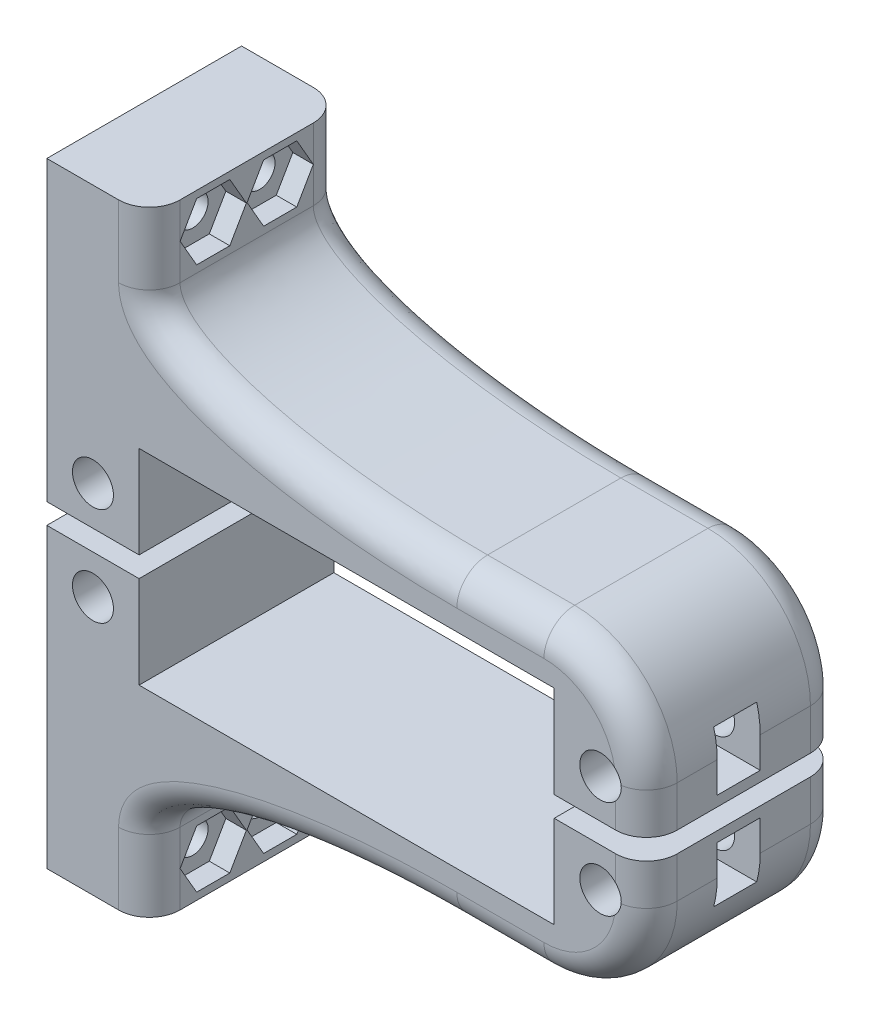
SolidWorks part; units mm, degrees
material "20% infill ABS"
ref_plane "Front" through (0, 0, 0) normal (0, 0, 1) x (1, 0, 0)
ref_plane "Top" through (0, 0, 0) normal (0, 1, 0) x (1, 0, 0)
ref_plane "Right" through (0, 0, 0) normal (1, 0, 0) x (0, 0, -1)
sketch "Sketch1" plane through (0, 0, 0) normal (0, 0, 1) x (1, 0, 0)
  line L1 (-9, -5) -> (49.5, -5)
  line L3 (-9, 25) -> (49.5, 25)
  line L4 (0, 0) -> (40.5, 0)
  line L5 (40.5, 0) -> (40.5, 20)
  line L6 (40.5, 20) -> (0, 20)
  line L7 (0, 20) -> (0, 0)
  line L8 (0, 0) -> (40.5, 0)
  line L9 (40.5, 0) -> (40.5, 20)
  line L10 (40.5, 20) -> (0, 20)
  line L11 (0, 20) -> (0, 0)
  line L12 (49.5, -5) -> (49.5, 25)
  line L13 (47.5, 20) -> (47.5, 0) construction
  line L17 (-9, 25) -> (-9, -5)
  dimension "D2" = 5
  dimension "D3" = 5
  dimension "D4" = 2
  dimension "D5" = 9
  dimension "D1" = 0
extrude "Boss-Extrude1" add sketch "Sketch1" against normal blind 19
ref_plane "Plane1" through (0, 0, -9) normal (0, 0, 1) x (1, 0, 0)
sketch "Sketch2" plane through (0, 0, -19) normal (0, 0, -1) x (-1, 0, 0)
  circle A0 centre (-45, 14.8) radius 2 construction
  circle A1 centre (-45, 5.2) radius 2 construction
  circle A2 centre (4.5, 14.8) radius 2 construction
  circle A3 centre (4.5, 5.2) radius 2 construction
  circle A4 centre (-45, 14.8) radius 2
  circle A5 centre (-45, 5.2) radius 2
  circle A6 centre (4.5, 14.8) radius 2
  circle A7 centre (4.5, 5.2) radius 2
extrude "Cut-Extrude1" cut sketch "Sketch2" against normal through all
sketch "Sketch3" plane through (0, 0, -9) normal (0, 0, 1) x (1, 0, 0)
  line L0 (49.5, 10) -> (-9, 10) construction
  line L7 (49.5, -5) -> (49.5, 25) construction
  line L8 (-9, 25) -> (-9, -5) construction
  line L9 (43.3834, 2.4) -> (41.7668, 5.2)
  line L10 (20.25, 20) -> (20.25, 0) construction
  line L13 (49.5, 17.6) -> (43.3834, 17.6)
  line L14 (41.7668, 5.2) -> (43.3834, 8)
  line L15 (43.3834, 17.6) -> (41.7668, 14.8)
  line L16 (41.7668, 14.8) -> (43.3834, 12)
  line L17 (43.3834, 12) -> (49.5, 12)
  line L28 (40.5, 20) -> (0, 20) construction
  line L29 (0, 0) -> (40.5, 0) construction
  line L30 (49.5, 17.6) -> (49.5, 12)
  line L33 (48.2332, 14.8) -> (47.4249, 16.2) [skipped]
  line L34 (46.6166, 12) -> (47.4249, 13.4) [skipped]
  line L35 (49.5, 17.6) -> (49.5, 12)
  line L36 (43.3834, 8) -> (49.5, 8)
  line L37 (49.5, 2.4) -> (49.5, 8)
  line L38 (49.5, 2.4) -> (43.3834, 2.4)
  line L39 (-1.2668, 14.8) -> (-2.8834, 12)
  line L40 (-2.8834, 17.6) -> (-1.2668, 14.8)
  line L41 (-9, 17.6) -> (-2.8834, 17.6)
  line L42 (-9, 17.6) -> (-9, 12)
  line L43 (-2.8834, 12) -> (-9, 12)
  line L44 (-2.8834, 8) -> (-9, 8)
  line L45 (-9, 2.4) -> (-9, 8)
  line L46 (-9, 2.4) -> (-2.8834, 2.4)
  line L47 (-2.8834, 2.4) -> (-1.2668, 5.2)
  line L48 (-1.2668, 5.2) -> (-2.8834, 8)
  circle A0 centre (45, 14.8) radius 2.8 construction
  dimension "D1" = 5.6
extrude "Cut-Extrude4" cut sketch "Sketch3" against normal mid plane 4.2 contours L43 L39 L40 L41 L42 | L47 L48 L44 L45 L46 | L38 L37 L36 L14 L9 | L30 L13 L15 L16 L17 | L41 L40 L39 L43 L42 region at (46.0218, 5.2, -9) region at (46.0218, 14.8, -9) region at (-5.5218, 14.8, -9) region at (-5.5218, 5.2, -9)
sketch "Sketch4" plane through (-9, 0, 0) normal (-1, 0, 0) x (0, 0, 1)
  line L0 (-19, 25) -> (-19, -5) construction
  line L1 (0, 25) -> (-19, 25)
  line L2 (0, 25) -> (0, 40)
  line L3 (0, 40) -> (-19, 40)
  line L4 (-19, 25) -> (-19, 40)
  dimension "D1" = 15
extrude "Boss-Extrude2" add sketch "Sketch4" against normal blind 10
fillet "Fillet1" radius 8 1 edges at (1, 25, -9.5) second distance 30 first distance on face at (1, 32.5, -9.5)
sketch "Sketch6" plane through (1, 0, 0) normal (1, 0, 0) x (0, 0, -1)
  line L0 (19, 36.5) -> (0, 36.5) construction
  line L1 (16, 36.5) -> (14.3834, 39.3)
  line L2 (14.3834, 39.3) -> (11.1503, 39.3)
  line L3 (11.1503, 39.3) -> (9.5337, 36.5)
  line L4 (9.5337, 36.5) -> (11.1503, 33.7)
  line L5 (11.1503, 33.7) -> (14.3834, 33.7)
  line L6 (14.3834, 33.7) -> (16, 36.5)
  line L7 (19, 40) -> (19, 33) construction
  line L8 (0, 33) -> (0, 40) construction
  line L9 (9.5, 40) -> (9.5, 33) construction
  line L10 (0, 40) -> (19, 40) construction
  line L11 (0, 33) -> (19, 33) construction
  line L12 (4.6166, 33.7) -> (3, 36.5)
  line L13 (7.8497, 33.7) -> (4.6166, 33.7)
  line L14 (9.4663, 36.5) -> (7.8497, 33.7)
  line L15 (7.8497, 39.3) -> (9.4663, 36.5)
  line L16 (4.6166, 39.3) -> (7.8497, 39.3)
  line L17 (3, 36.5) -> (4.6166, 39.3)
  circle A0 centre (12.7668, 36.5) radius 1.5
  circle A1 centre (12.7668, 36.5) radius 2.8 construction
  circle A2 centre (6.2332, 36.5) radius 1.5
  dimension "D2" = 3
  dimension "D1" = 5.6
  dimension "D3" = 3
extrude "Cut-Extrude5" cut sketch "Sketch6" against normal through all contours A0 | A2
extrude "Cut-Extrude6" cut sketch "Sketch6<4>" against normal blind 2
sketch "Sketch6<4>" plane through (1, 0, 0) normal (1, 0, 0) x (0, 0, -1) same geometry as "Sketch6"
ref_plane "Plane2" through (0, 10, 0) normal (0, 1, 0) x (1, 0, 0)
mirror "Mirror2" about plane through (0, 10, 0) normal (0, 1, 0) of "Cut-Extrude5", "Cut-Extrude6", "Boss-Extrude2"
fillet "Fillet2" radius 30 1 edges at (1, -5, -9.5) second distance 8 first distance on face at (25.25, -5, -9.5)
fillet "Fillet3" radius 10 2 edges at (49.5, -5, -9.5) (49.5, 25, -9.5)
fillet "Fillet4" radius 3 9 edges at (46.5711, 22.0711, -19) (49.5, 10, -19) (46.5711, -2.0711, -19)
fillet "Fillet5" radius 3 9 edges at (46.5711, 22.0711, 0) (46.5711, -2.0711, 0) (49.5, 10, 0)
sketch "Sketch7" plane through (0, 0, 0) normal (0, 0, 1) x (1, 0, 0)
  line L1 (53.9196, 11) -> (-14.7387, 11)
  line L2 (53.9196, 11) -> (53.9196, 9)
  line L3 (53.9196, 9) -> (-14.7387, 9)
  line L4 (-14.7387, 11) -> (-14.7387, 9)
  line L5 (10.45, 10) -> (-10.45, 10) construction
  point P4 (53.9196, 10)
  point P6 (53.9196, 8.0829)
  dimension "D1" = 2
extrude "Cut-Extrude7" cut sketch "Sketch7" against normal through all
